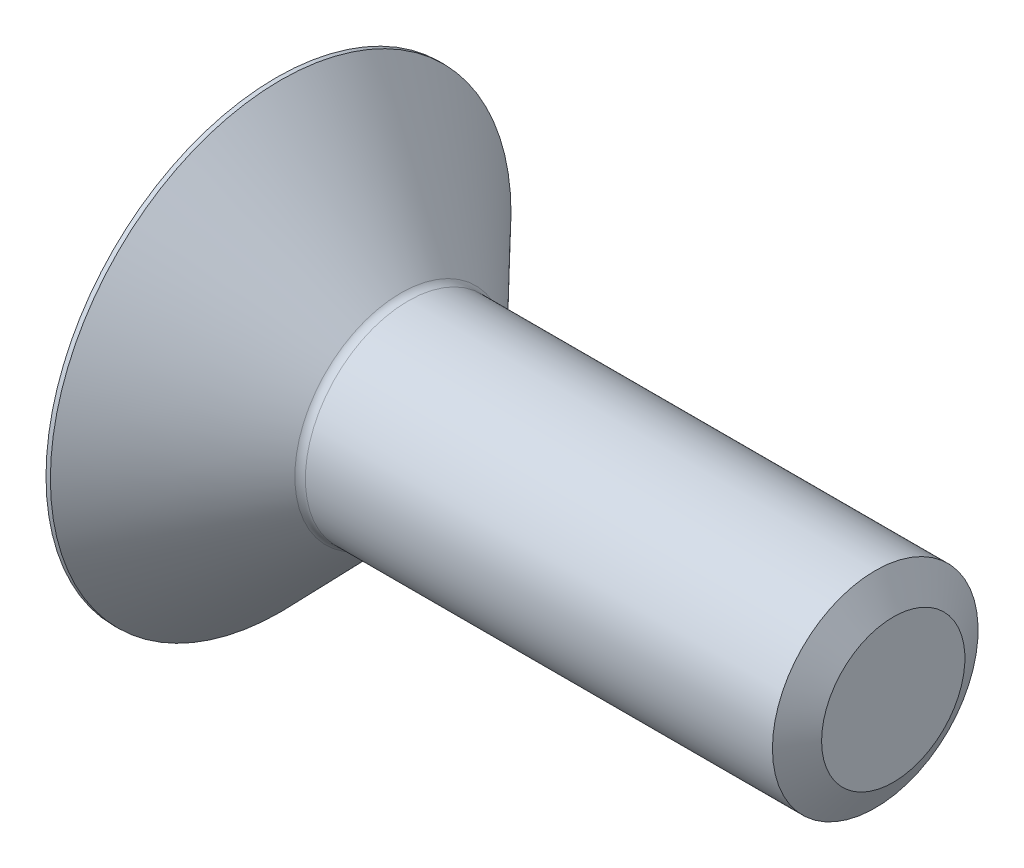
SolidWorks part; units mm, degrees
ref_plane "前视基准面" through (0, 0, 0) normal (0, 0, 1) x (1, 0, 0)
ref_plane "上视基准面" through (0, 0, 0) normal (0, 1, 0) x (1, 0, 0)
ref_plane "右视基准面" through (0, 0, 0) normal (1, 0, 0) x (0, 0, -1)
sketch "尺寸草图" plane through (0, 0, 0) normal (0, 0, 1) x (1, 0, 0)
  line L0 (0, 0) -> (12, 0) construction
  line L1 (12, 0) -> (12, 2) construction
  line L2 (12, 2) -> (11.3, 2) construction
  line L3 (11.3, 2) -> (4, 2) construction
  line L4 (0, 4.48) -> (2.48, 4.48) construction
  line L5 (2.48, 4.48) -> (2.68, 4.48) construction
  point P3 (12, 2.2)
  point P7 (0, 4.48)
  point P8 (0, 2)
  point P9 (0, 2.87)
  point P13 (0, 1.25)
  point P15 (1.5, 4.48)
  point P16 (2.23, 4.48)
  dimension "l" = 12
  dimension "d" = 4
  dimension "P" = 0.7
  dimension "b" = 8
  dimension "da" = 4.4
  dimension "dk" = 8.96
  dimension "ds" = 4
  dimension "e" = 2.87
  dimension "k" = 2.48
  dimension "r" = 0.2
  dimension "s" = 2.5
  dimension "t" = 1.5
  dimension "w" = 0.45
sketch "草图1" plane through (0, 0, 0) normal (0, 0, 1) x (1, 0, 0)
  line L0 (0, 2) -> (-9.4351, 2)
  line L1 (-9.579, 2.0611) -> (-11.9149, 4.48)
  line L2 (-11.9149, 4.48) -> (-12, 4.48)
  line L3 (-12, 4.48) -> (-12, 0)
  line L4 (-12, 0) -> (0, 0)
  line L5 (0, 0) -> (0, 2)
  line L6 (0, 0) -> (-12, 0) construction
  arc A0 (-9.4351, 2) -> (-9.579, 2.0611) centre (-9.4351, 2.2) cw
  point P9 (-9.52, 2)
  dimension "r" = 0.2
  dimension "k" = 2.48
  dimension "dk" = 8.96
  dimension "l" = 12
  dimension "D5" = 46
  dimension "d" = 4
revolve "旋转1" add sketch "草图1" angle 360 about L6
cosmetic thread "装饰螺纹线1" parameters "b"=8, "D2"=3.2
sketch "草图2" plane through (-12, 0, 0) normal (-1, 0, 0) x (0, 0, 1)
  line L0 (0, 0) -> (0, 2) construction
  line L1 (0, 1.4434) -> (-1.25, 0.7217)
  line L2 (-1.25, 0.7217) -> (-1.25, -0.7217)
  line L3 (-1.25, -0.7217) -> (0, -1.4434)
  line L4 (0, -1.4434) -> (1.25, -0.7217)
  line L5 (1.25, -0.7217) -> (1.25, 0.7217)
  line L6 (1.25, 0.7217) -> (0, 1.4434)
  circle A0 centre (0, 0) radius 1.25 construction
  point P1 (0, 1.4266)
  dimension "s" = 2.5
  dimension "e" = 2.87
extrude "切除-拉伸1" cut sketch "草图2" against normal blind 2.48
sketch "草图6" plane through (0, 0, 0) normal (0, 0, 1) x (1, 0, 0)
  line L0 (-10.5, 1.4434) -> (-9.6667, 0)
  line L1 (-9.6667, 0) -> (-9.15, 0)
  line L2 (-9.15, 0) -> (-9.15, 1.4434)
  line L3 (-9.15, 1.4434) -> (-10.5, 1.4434)
  line L4 (-12, 0) -> (-9.52, 0) construction
  line L5 (-12, 0) -> (-14.87, 0) construction
  dimension "D1" = 60
  dimension "t" = 1.5
  dimension "t1" = 2.48
  dimension "e-s" = 0.37
  dimension "e" = 2.87
revolve "旋转2" add sketch "草图6" angle 360 about L4
sketch "草图7" plane through (0, 0, 0) normal (0, 0, 1) x (1, 0, 0)
  line L0 (-12, 1.4434) -> (-12, 0)
  line L1 (-12, 0) -> (-11.63, 0)
  line L2 (-11.63, 0) -> (-12, 1.4434)
  line L3 (-12, 0) -> (-11.63, 0) construction
  dimension "e-s*1.1" = 0.37
revolve "切除-旋转2" cut sketch "草图7" angle 360 about L3
sketch "草图4" plane through (0, 0, 0) normal (0, 0, 1) x (1, 0, 0)
  line L0 (-0.35, 2) -> (0, 1.3938)
  line L1 (0, -2) -> (0, 2) construction
  line L2 (0, 1.3938) -> (0.35, 2)
  line L3 (0.35, 2) -> (-0.35, 2)
  line L4 (-0.35, 0) -> (0.35, 0) construction
  dimension "d" = 4
  dimension "p" = 0.7
revolve "切除-旋转1" cut sketch "草图4" angle 360 about L4
ref_axis "基准轴1" through (-21.1715, 0, 0) along (1, 0, 0)
pattern_linear "阵列(线性)2" [suppressed] count 11 spacing 0.7 along (-1, 0, 0) of bodies 104
